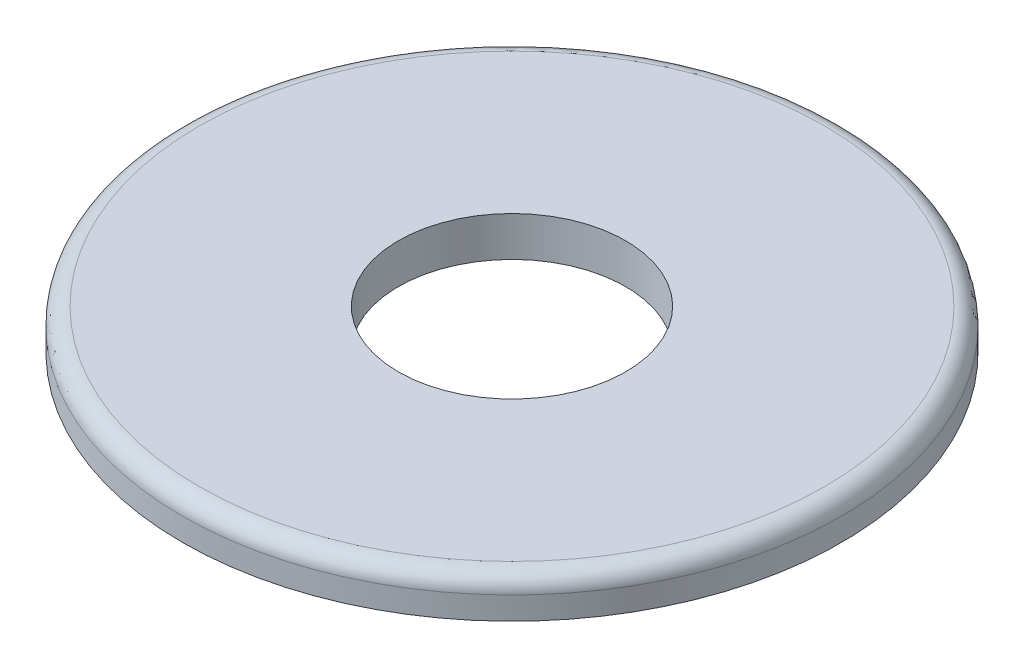
SolidWorks part; units mm, degrees
ref_plane "Front Plane" through (0, 0, 0) normal (0, 0, 1) x (1, 0, 0)
ref_plane "Top Plane" through (0, 0, 0) normal (0, 1, 0) x (1, 0, 0)
ref_plane "Right Plane" through (0, 0, 0) normal (1, 0, 0) x (0, 0, -1)
sketch "Sketch1" plane through (0, 0, 0) normal (0, 1, 0) x (1, 0, 0)
  circle A0 centre (0, 0) radius 184.15
  circle A1 centre (0, 0) radius 63.5
  dimension "D1" = 368.3
extrude "Boss-Extrude1" add sketch "Sketch1" along normal blind 22.225
fillet "Fillet1" radius 9.525 1 edges at (0, 22.225, 184.15)
